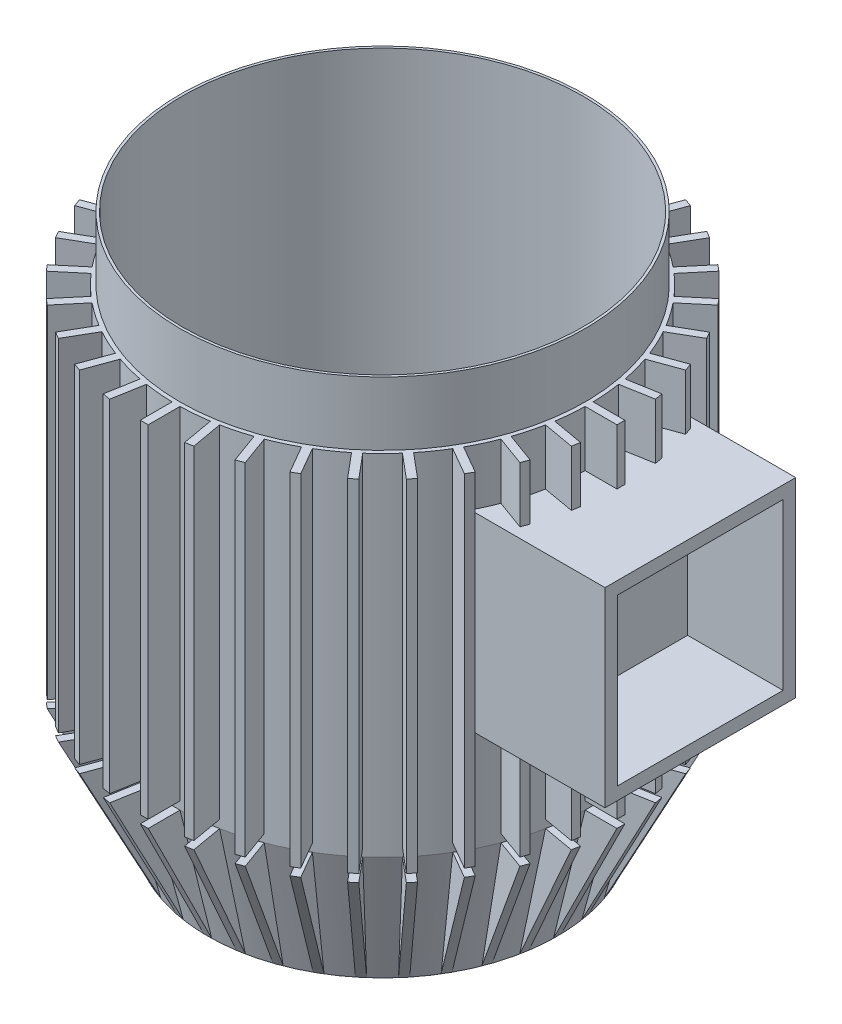
SolidWorks part; units mm, degrees
ref_plane "Front Plane" through (0, 0, 0) normal (0, 0, 1) x (1, 0, 0)
ref_plane "Top Plane" through (0, 0, 0) normal (0, 1, 0) x (1, 0, 0)
ref_plane "Right Plane" through (0, 0, 0) normal (1, 0, 0) x (0, 0, -1)
sketch "Sketch2" plane through (0, 0, 0) normal (0, 1, 0) x (1, 0, 0)
  circle A0 centre (0, 0) radius 6.5
  dimension "D1" = 13
extrude "Boss-Extrude1" add sketch "Sketch2" against normal blind 17
ref_plane "Plane1" through (0, 0, 7.5) normal (0, 0, 1) x (1, 0, 0)
chamfer "Chamfer3" distance 1 distance2 4 1 edges at (0, -17, 6.5) first distance on face at (0, -17, 6.5)
shell "Shell2" thickness 0.2 removed face at (0, 0, 6.5)
sketch "Sketch4" plane through (0, 0, 7.5) normal (0, 0, 1) x (1, 0, 0)
  line L0 (6.5, 0) -> (-6.5, 0) construction
  line L1 (-0.125, 0) -> (0.125, 0)
  line L2 (-0.125, 0) -> (-0.125, -17)
  line L3 (-0.125, -17) -> (0.125, -17)
  line L4 (0.125, 0) -> (0.125, -17)
  line L5 (-5.5, -17) -> (5.5, -17) construction
  line L6 (0, 0) -> (0, -18.426) construction
  dimension "D1" = 0.25
extrude "Boss-Extrude2" add sketch "Sketch4" against normal up to next
pattern_circular "CirPattern1" count 36 over 360 about axis through (0, -17, 0) along (0, 1, 0) of "Boss-Extrude2" reverse direction yes
sketch "Sketch5" plane through (0, 0, 0) normal (0, 0, 1) x (1, 0, 0)
  line L0 (7.5, -13) -> (5.4986, -17)
  line L1 (7.5, -17) -> (7.5, 0) construction
  line L2 (5.4986, -17) -> (7.9986, -17.75)
  line L3 (7.9986, -17.75) -> (7.9986, -12.75)
  line L4 (7.9986, -12.75) -> (6.5, -12.75)
  line L5 (6.5, -12.75) -> (6.5, -13)
  line L6 (6.5, -13) -> (7.5, -13)
  line L11 (0, 0) -> (0, -20) construction
  dimension "D1" = 0.25
  dimension "D2" = 2.5
  dimension "D3" = 5
  dimension "D4" = 4
  dimension "D5" = 20
  dimension "D6" = 6.5
revolve "Cut-Revolve1" cut sketch "Sketch5" angle 360 about L11
sketch "Sketch6" plane through (0, -17, 0) normal (0, -1, 0) x (1, 0, 0)
  circle A0 centre (0, 0) radius 1
  dimension "D1" = 2
extrude "Cut-Extrude1" cut sketch "Sketch6" against normal through all contours A0
ref_plane "Plane2" through (10, 0, 0) normal (1, 0, 0) x (0, 0, -1)
sketch "Sketch7" plane through (10, 0, 0) normal (1, 0, 0) x (0, 0, -1)
  line L1 (-3, -3.75) -> (3, -3.75)
  line L2 (-3, -3.75) -> (-3, -9.75)
  line L3 (-3, -9.75) -> (3, -9.75)
  line L4 (3, -3.75) -> (3, -9.75)
  line L5 (0, 0) -> (0, -20) construction
  line L6 (-5.665, -12.75) -> (-4.898, -12.75) construction
  dimension "D1" = 6
  dimension "D2" = 6
  dimension "D3" = 20
  dimension "D4" = 3
extrude "Boss-Extrude3" add sketch "Sketch7" against normal up to next
sketch "Sketch8" plane through (10, 0, 0) normal (1, 0, 0) x (0, 0, -1)
  line L8 (-2.6, -4.15) -> (-2.6, -9.35)
  line L9 (-2.6, -9.35) -> (2.6, -9.35)
  line L10 (2.6, -9.35) -> (2.6, -4.15)
  line L11 (2.6, -4.15) -> (-2.6, -4.15)
  line L12 (-2.6, -4.15) -> (-2.6, -9.35)
  line L13 (-2.6, -9.35) -> (2.6, -9.35)
  line L14 (2.6, -9.35) -> (2.6, -4.15)
  line L15 (2.6, -4.15) -> (-2.6, -4.15)
  line L16 (-3, -3.75) -> (-3, -9.75)
  line L17 (-3, -9.75) -> (3, -9.75)
  line L18 (3, -9.75) -> (3, -3.75)
  line L19 (3, -3.75) -> (-3, -3.75)
  line L20 (-3, -3.75) -> (-3, -9.75)
  line L21 (-3, -9.75) -> (3, -9.75)
  line L22 (3, -9.75) -> (3, -3.75)
  line L23 (3, -3.75) -> (-3, -3.75)
  dimension "D1" = 0.4
  dimension "D2" = 0
extrude "Cut-Extrude10" cut sketch "Sketch8" against normal blind 3 contours L14 L15 L12 L13 region at (10, -6.75, 0)
sketch "Sketch9" plane through (0, 0, 0) normal (1, 0, 0) x (0, 0, -1)
  line L0 (-6.3784, -12.75) -> (-6.3784, 0) construction
  line L1 (-8, 0) -> (-6.3784, 0)
  line L2 (-8, 0) -> (-8, -2)
  line L3 (-8, -2) -> (-6.3784, -2)
  line L4 (-6.3784, 0) -> (-6.3784, -2)
  line L5 (0, 0) -> (0, -4.3629) construction
  line L6 (6.3, 0) -> (-6.3, 0) construction
  dimension "D1" = 2
  dimension "D2" = 8
revolve "Cut-Revolve2" cut sketch "Sketch9" angle 360 about L5
